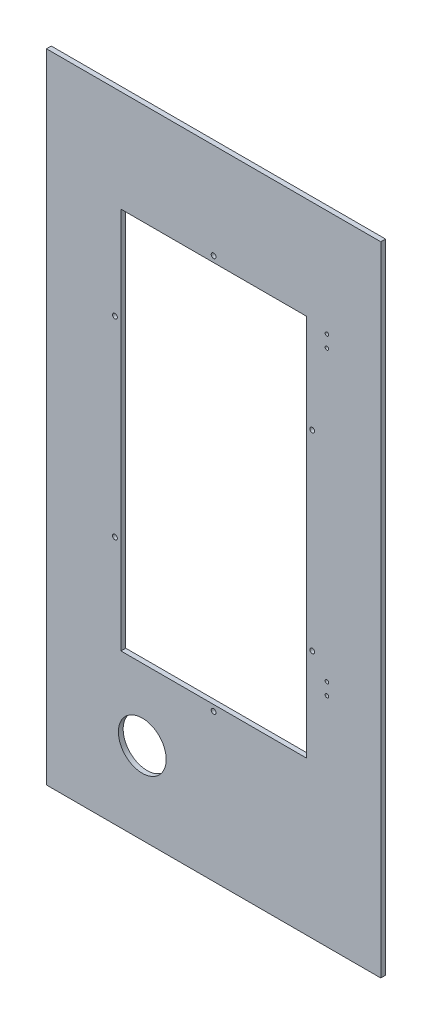
SolidWorks part; units mm, degrees
ref_plane "Спереди" through (0, 0, 0) normal (0, 0, 1) x (1, 0, 0)
ref_plane "Сверху" through (0, 0, 0) normal (0, 1, 0) x (1, 0, 0)
ref_plane "Справа" through (0, 0, 0) normal (1, 0, 0) x (0, 0, -1)
sketch "Эскиз1" plane through (0, 0, 0) normal (0, 1, 0) x (1, 0, 0)
  line L1 (-144.7882, -1.3414) -> (134.7883, -1.3414)
  line L2 (-144.7882, -1.3414) -> (-144.7882, -5.3414)
  line L3 (-144.7882, -5.3414) -> (134.7883, -5.3414)
  line L4 (134.7883, -1.3414) -> (134.7883, -5.3414)
  dimension "D1" = 4
extrude "Вытянуть1" add sketch "Эскиз1" along normal up to surface (533.2137 mm away)
sketch "Эскиз2" plane through (0, 0, 1.3414) normal (0, 0, -1) x (-1, 0, 0)
  circle A0 centre (64.6516, 68.5542) radius 20
extrude "Вырез-Вытянуть1" cut sketch "Эскиз2" against normal through all
sketch "Sketch1" plane through (0, 0, 1.3414) normal (0, 0, -1) x (-1, 0, 0)
  line L0 (-201.6101, 448.2137) -> (228.2599, 448.2137) construction
  line L3 (-351.4591, 128.2137) -> (303.9412, 128.2137) construction
  line L4 (-134.7883, 533.2137) -> (144.7882, 533.2137) construction
  line L5 (5, 533.2137) -> (5, 456.8501) construction
  line L6 (-238.6939, 288.2137) -> (-171.3376, 288.2137) construction
  line L9 (-72.5, 448.2137) -> (82.5, 448.2137)
  line L10 (-72.5, 448.2137) -> (-72.5, 128.2137)
  line L11 (-72.5, 128.2137) -> (82.5, 128.2137)
  line L12 (82.5, 448.2137) -> (82.5, 128.2137)
  line L13 (-72.5, 448.2137) -> (82.5, 128.2137) construction
  line L14 (-72.5, 128.2137) -> (82.5, 448.2137) construction
  point P9 (5, 288.2137)
  dimension "D1" = 320
  dimension "D2" = 85
  dimension "D3" = 160
extrude "Cut-Extrude1" cut sketch "Sketch1" against normal through all contours L10 L11 L12 L9
sketch "Sketch2" plane through (0, 0, 5.3414) normal (0, 0, 1) x (1, 0, 0)
  line L0 (-82.5, 448.2137) -> (-82.5, 128.2137) construction
  line L1 (72.5, 448.2137) -> (-82.5, 448.2137) construction
  line L2 (-82.5, 288.2137) -> (-125.5991, 288.2137) construction
  line L3 (-5, 127.0553) -> (-5, 276.1441) construction
  circle A0 centre (-87.5, 368.2137) radius 2
  circle A1 centre (-87.5, 208.2137) radius 2
  circle A2 centre (77.5, 208.2137) radius 2
  circle A3 centre (77.5, 368.2137) radius 2
  circle A4 centre (-5, 453.2137) radius 2
  circle A5 centre (-5, 123.2137) radius 2
  circle A6 centre (89.7398, 443.8535) radius 1.5
  circle A7 centre (89.7398, 433.681) radius 1.5
  circle A8 centre (89.7398, 192.0819) radius 1.5
  circle A9 centre (89.7398, 181.9094) radius 1.5
  dimension "D1" = 5
  dimension "D3" = 5
  dimension "D2" = 80
extrude "Cut-Extrude2" cut sketch "Sketch2" against normal through all
